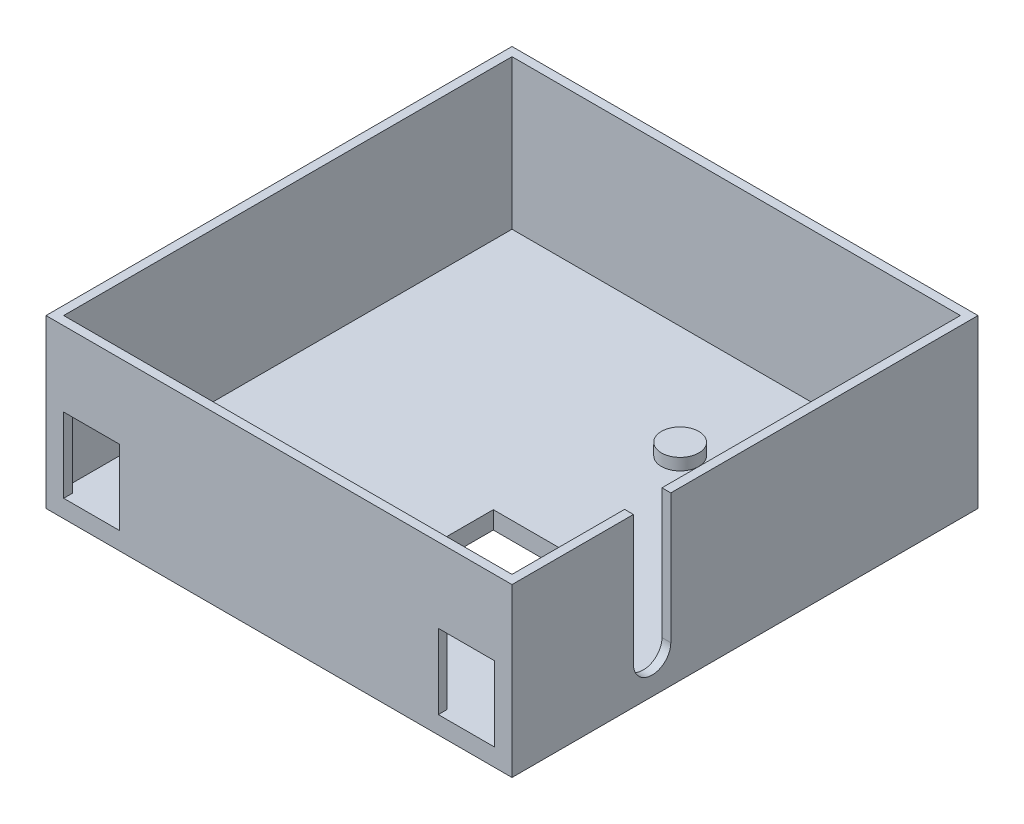
SolidWorks part; units mm, degrees
ref_plane "Front Plane" through (0, 0, 0) normal (0, 0, 1) x (1, 0, 0)
ref_plane "Top Plane" through (0, 0, 0) normal (0, 1, 0) x (1, 0, 0)
ref_plane "Right Plane" through (0, 0, 0) normal (1, 0, 0) x (0, 0, -1)
sketch "Sketch1" plane through (0, 0, 0) normal (0, 1, 0) x (1, 0, 0)
  line L1 (-39.6, -39.6) -> (39.6, -39.6)
  line L2 (-39.6, -39.6) -> (-39.6, 39.6)
  line L3 (-39.6, 39.6) -> (39.6, 39.6)
  line L4 (39.6, -39.6) -> (39.6, 39.6)
  line L5 (-39.6, -39.6) -> (39.6, 39.6) construction
  line L6 (-39.6, 39.6) -> (39.6, -39.6) construction
  point P0 (0, 0)
  dimension "D1" = 79.2
  dimension "D2" = 79.2
extrude "Boss-Extrude1" add sketch "Sketch1" along normal blind 3
sketch "Sketch2" plane through (0, 3, 0) normal (0, 1, 0) x (1, 0, 0)
  line L1 (-39.6, -39.6) -> (39.6, -39.6)
  line L2 (-39.6, -39.6) -> (-39.6, 39.6)
  line L3 (-39.6, 39.6) -> (39.6, 39.6)
  line L4 (39.6, -39.6) -> (39.6, 39.6)
  line L5 (-39.6, -39.6) -> (39.6, 39.6) construction
  line L6 (-39.6, 39.6) -> (39.6, -39.6) construction
  line L7 (-38.1, -38.1) -> (38.1, -38.1)
  line L8 (-38.1, -38.1) -> (-38.1, 38.1)
  line L9 (-38.1, 38.1) -> (38.1, 38.1)
  line L10 (38.1, -38.1) -> (38.1, 38.1)
  line L11 (-38.1, -38.1) -> (38.1, 38.1) construction
  line L12 (-38.1, 38.1) -> (38.1, -38.1) construction
  point P0 (0, 0)
  point P7 (0, 0)
  dimension "D1" = 76.2
  dimension "D2" = 76.2
extrude "Boss-Extrude2" add sketch "Sketch2" along normal blind 25.4
sketch "Sketch3" plane through (39.6, 0, 0) normal (1, 0, 0) x (0, 0, -1)
  line L0 (-39.6, 28.4) -> (-39.6, 0) construction
  line L1 (-39.6, 0) -> (39.6, 0) construction
  line L2 (-12.6125, 6.35) -> (-12.6125, 28.4)
  line L3 (-39.6, 28.4) -> (39.6, 28.4) construction
  line L4 (-12.6125, 28.4) -> (-18.9625, 28.4)
  line L5 (-18.9625, 28.4) -> (-18.9625, 6.35)
  circle A0 centre (-15.7875, 6.35) radius 3.175
  line M3 (39.6, 28.4) -> (-39.6, 28.4)
  dimension "D3" = 6.35
  dimension "D1" = 23.8125
  dimension "D2" = 6.35
extrude "Cut-Extrude2" cut sketch "Sketch3" against normal blind 19.05 contours A0 | A0 L2 L5 M3 region at (39.6, 18.609, 15.7875) region at (39.6, 6.35, 15.7875)
sketch "Sketch5" plane through (0, 0, 39.6) normal (0, 0, 1) x (1, 0, 0)
  line L0 (39.6, 28.4) -> (39.6, 0) construction
  line L1 (27.075, 3) -> (36.6, 3)
  line L2 (27.075, 3) -> (27.075, 15.7)
  line L3 (27.075, 15.7) -> (36.6, 15.7)
  line L4 (36.6, 3) -> (36.6, 15.7)
  line L5 (27.075, 3) -> (36.6, 15.7) construction
  line L6 (27.075, 15.7) -> (36.6, 3) construction
  line L7 (-39.6, 0) -> (39.6, 0) construction
  line L8 (-39.6, 28.4) -> (-39.6, 0) construction
  line L9 (-36.6, 15.7) -> (-27.075, 15.7)
  line L10 (-36.6, 15.7) -> (-36.6, 3)
  line L11 (-36.6, 3) -> (-27.075, 3)
  line L12 (-27.075, 15.7) -> (-27.075, 3)
  line L13 (-36.6, 15.7) -> (-27.075, 3) construction
  line L14 (-36.6, 3) -> (-27.075, 15.7) construction
  point P0 (31.8375, 9.35)
  point P9 (-31.8375, 9.35)
  dimension "D1" = 12.7
  dimension "D2" = 9.525
  dimension "D3" = 3
  dimension "D4" = 3
  dimension "D5" = 12.7
  dimension "D6" = 9.525
  dimension "D7" = 3
  dimension "D8" = 3
extrude "Cut-Extrude3" cut sketch "Sketch5" against normal blind 19.05
sketch "Sketch6" plane through (0, 3, 0) normal (0, 1, 0) x (1, 0, 0)
  line L0 (38.1, -38.1) -> (38.1, 38.1) construction
  line L1 (38.1, 38.1) -> (-38.1, 38.1) construction
  circle A0 centre (9.525, 19.05) radius 3.175
  dimension "D3" = 6.35
  dimension "D1" = 28.575
  dimension "D2" = 19.05
extrude "Boss-Extrude3" add sketch "Sketch6" along normal blind 2
sketch "Sketch7" plane through (0, 3, 0) normal (0, 1, 0) x (1, 0, 0)
  line L0 (-38.1, -38.1) -> (-36.6, -38.1) construction
  line L1 (1.5875, -17.4625) -> (14.2875, -17.4625)
  line L2 (1.5875, -17.4625) -> (1.5875, -4.7625)
  line L3 (1.5875, -4.7625) -> (14.2875, -4.7625)
  line L4 (14.2875, -17.4625) -> (14.2875, -4.7625)
  line L5 (1.5875, -17.4625) -> (14.2875, -4.7625) construction
  line L6 (1.5875, -4.7625) -> (14.2875, -17.4625) construction
  line L7 (38.1, -38.1) -> (38.1, 38.1) construction
  point P0 (7.9375, -11.1125)
  dimension "D1" = 12.7
  dimension "D2" = 12.7
  dimension "D3" = 26.9875
  dimension "D4" = 30.1625
extrude "Cut-Extrude5" cut sketch "Sketch7" against normal blind 26
